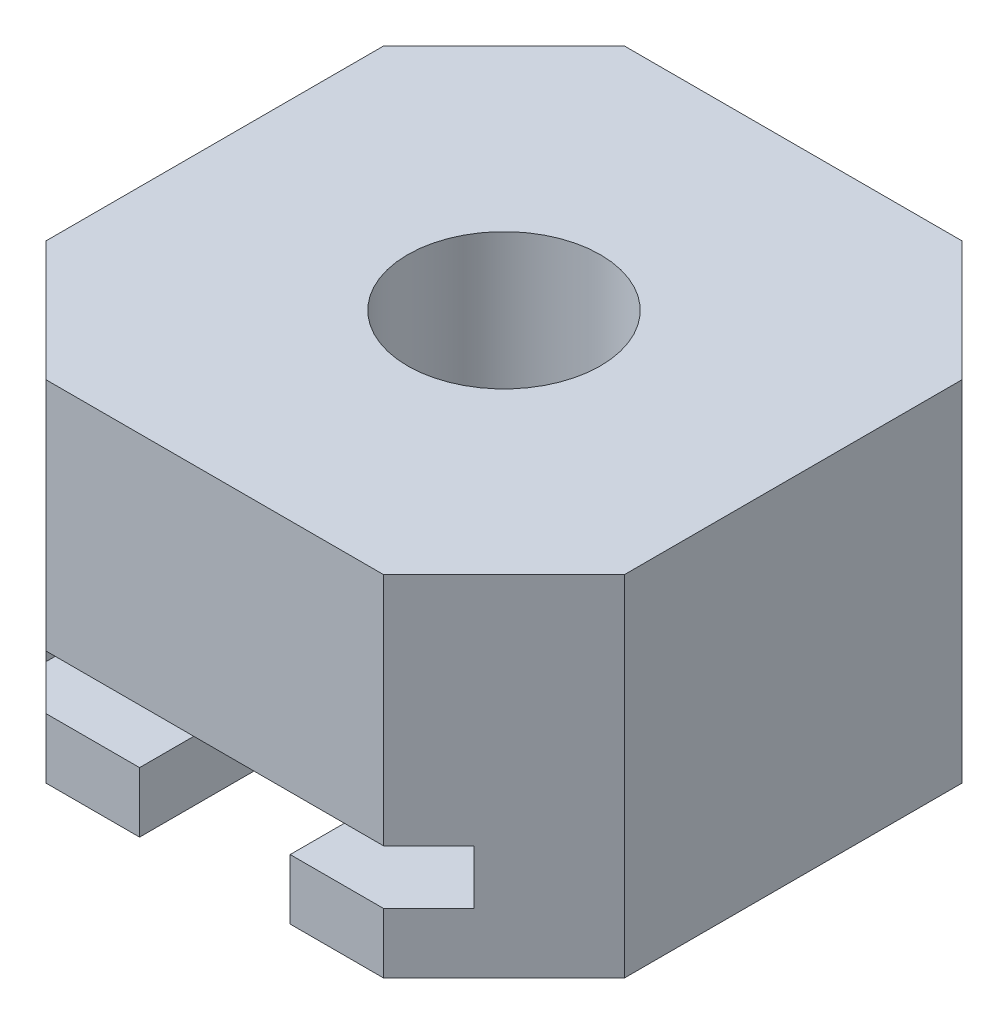
SolidWorks part; units mm, degrees
ref_plane "Front Plane" through (0, 0, 0) normal (0, 0, 1) x (1, 0, 0)
ref_plane "Top Plane" through (0, 0, 0) normal (0, 1, 0) x (1, 0, 0)
ref_plane "Right Plane" through (0, 0, 0) normal (1, 0, 0) x (0, 0, -1)
sketch "Sketch1" plane through (0, 0, 0) normal (0, 1, 0) x (1, 0, 0)
  line L0 (-9.017, 0) -> (9.017, 0) construction
  line L1 (0, 9.017) -> (0, -9.017) construction
  line L2 (-6.096, 9.017) -> (6.096, 9.017)
  line L3 (6.096, 9.017) -> (9.017, 6.096)
  line L4 (9.017, 6.096) -> (9.017, -6.096)
  line L5 (9.017, -6.096) -> (6.096, -9.017)
  line L6 (6.096, -9.017) -> (-6.096, -9.017)
  line L7 (-6.096, -9.017) -> (-9.017, -6.096)
  line L8 (-9.017, -6.096) -> (-9.017, 6.096)
  line L9 (-9.017, 6.096) -> (-6.096, 9.017)
  line L10 (6.096, 9.017) -> (6.096, -9.017) construction
  line L11 (9.017, 6.096) -> (-9.017, 6.096) construction
  line L12 (-12.192, 12.192) -> (-12.192, -12.192)
  line L13 (-12.192, -12.192) -> (12.192, -12.192)
  line L14 (12.192, -12.192) -> (12.192, 12.192)
  line L15 (12.192, 12.192) -> (-12.192, 12.192)
  point P0 (0, 0)
  dimension "D1" = 12.192
  dimension "D2" = 45
  dimension "D3" = 18.034
  dimension "D4" = 3.175
  dimension "D5" = 3.175
  dimension "D6" = 3.175
  dimension "D7" = 3.175
extrude "Boss-Extrude1" add sketch "Sketch1" along normal blind 12.192
sketch "Sketch2" plane through (0, 0, 0) normal (0, -1, 0) x (1, 0, 0)
  line L1 (12.192, 12.192) -> (-12.192, 12.192)
  line L2 (12.192, 12.192) -> (12.192, -12.192)
  line L3 (12.192, -12.192) -> (-12.192, -12.192)
  line L4 (-12.192, 12.192) -> (-12.192, -12.192)
  line L5 (12.192, 12.192) -> (-12.192, -12.192) construction
  line L6 (12.192, -12.192) -> (-12.192, 12.192) construction
  circle A0 centre (0, 0) radius 3.175
  point P4 (0, 0)
  dimension "D1" = 6.35
extrude "Boss-Extrude2" add sketch "Sketch2" along normal blind 2.54
sketch "Sketch3" plane through (0, -2.54, 0) normal (0, -1, 0) x (1, 0, 0)
  line L0 (12.192, 12.192) -> (-12.192, 12.192) construction
  line L1 (-3.175, 0) -> (3.175, 0)
  line L2 (-3.175, 0) -> (-3.175, 12.192)
  line L3 (-3.175, 12.192) -> (3.175, 12.192)
  line L4 (3.175, 0) -> (3.175, 12.192)
  line L5 (-3.175, 0) -> (3.175, 12.192) construction
  line L6 (-3.175, 12.192) -> (3.175, 0) construction
  line L7 (0, 0) -> (-3.175, 0) construction
  circle A0 centre (0, 0) radius 3.175 construction
  point P4 (0, 6.096)
extrude "Cut-Extrude1" cut sketch "Sketch3" against normal up to surface (2.54 mm away) up to face at (0, 0, 0)
sketch "Sketch4" plane through (0, 0, 0) normal (0, 1, 0) x (1, 0, 0)
  line L1 (-9.017, -6.096) -> (9.017, -6.096)
  line L2 (-9.017, -6.096) -> (-9.017, -12.192)
  line L3 (-9.017, -12.192) -> (9.017, -12.192)
  line L4 (9.017, -6.096) -> (9.017, -12.192)
  line L5 (-9.017, -6.096) -> (9.017, -12.192) construction
  line L6 (-9.017, -12.192) -> (9.017, -6.096) construction
  line L7 (-3.175, -12.192) -> (-12.192, -12.192) construction
  point P4 (0, -9.144)
  line M5 (-3.175, -9.017) -> (-3.175, 0)
  line M7 (3.175, 0) -> (3.175, -9.017)
  line M8 (3.175, -9.017) -> (6.096, -9.017)
  line M9 (6.096, -9.017) -> (9.017, -6.096)
  line M15 (-9.017, -6.096) -> (-6.096, -9.017)
  line M16 (-6.096, -9.017) -> (-3.175, -9.017)
extrude "Cut-Extrude2" cut sketch "Sketch4" along normal blind 2.286 contours L1 M15 M16 M5 | L4 L1 L2 L3 M9 M8 M7 M5 M16 M15 | L1 M7 M8 M9 region at (0, 0, 9.6751) region at (-5.4469, 0, 7.3942) region at (5.4469, 0, 7.3942)
sketch "Sketch5" plane through (0, 12.192, 0) normal (0, 1, 0) x (1, 0, 0)
  line L1 (12.192, 12.192) -> (-12.192, 12.192)
  line L2 (12.192, 12.192) -> (12.192, -12.192)
  line L3 (12.192, -12.192) -> (-12.192, -12.192)
  line L4 (-12.192, 12.192) -> (-12.192, -12.192)
  line L5 (12.192, 12.192) -> (-12.192, -12.192) construction
  line L6 (12.192, -12.192) -> (-12.192, 12.192) construction
  circle A0 centre (0, 0) radius 4.064
  point P0 (0, 0)
  dimension "D1" = 8.128
extrude "Boss-Extrude3" add sketch "Sketch5" against normal up to surface (9.906 mm away) up to face at (0, 2.286, 9.1017)
chamfer "Chamfer1" distance 5.08 angle 45 4 edges at (12.192, 4.826, -12.192) (-12.192, 4.826, -12.192) (-12.192, 4.826, 12.192) (12.192, 4.826, 12.192)
